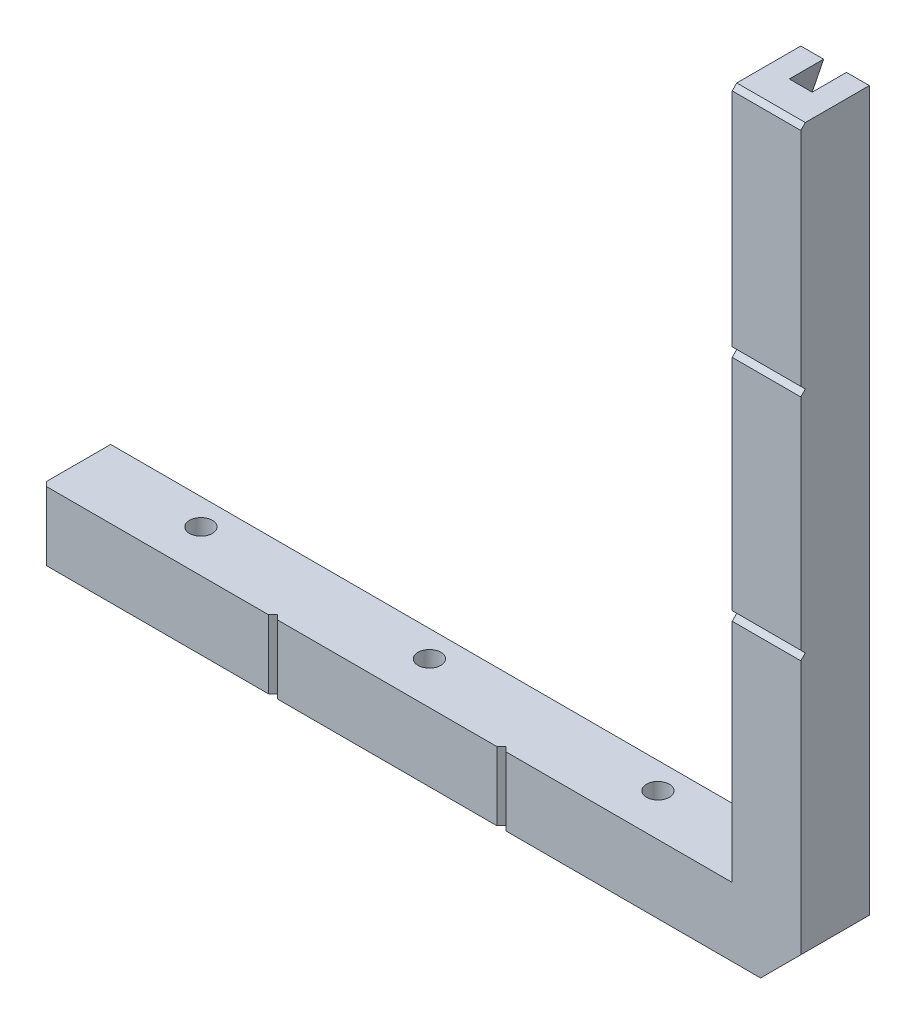
SolidWorks part; units mm, degrees
ref_plane "Front Plane" through (0, 0, 0) normal (0, 0, 1) x (1, 0, 0)
ref_plane "Top Plane" through (0, 0, 0) normal (0, 1, 0) x (1, 0, 0)
ref_plane "Right Plane" through (0, 0, 0) normal (1, 0, 0) x (0, 0, -1)
sketch "Sketch1" plane through (0, 0, 0) normal (0, 0, 1) x (1, 0, 0)
  line L0 (0, 0) -> (0, 151)
  line L1 (0, 151) -> (15, 151)
  line L2 (15, 151) -> (15, -15)
  line L3 (15, -15) -> (-151, -15)
  line L4 (-151, -15) -> (-151, 0)
  line L5 (-151, 0) -> (0, 0)
  dimension "D1" = 15
  dimension "D2" = 15
  dimension "D3" = 151
  dimension "D4" = 151
extrude "Boss-Extrude1" add sketch "Sketch1" along normal blind 15
sketch "Sketch3" plane through (0, 0, 15) normal (0, 0, 1) x (1, 0, 0)
  line L0 (-151, -7.5) -> (15, -7.5) construction
  line L1 (-151, 0) -> (-151, -15) construction
  line L2 (15, -15) -> (15, 151) construction
  line L3 (7.5, 151) -> (7.5, -15) construction
  line L4 (15, 151) -> (0, 151) construction
  line L5 (-151, -15) -> (15, -15) construction
  line L6 (0, 0) -> (-151, 0) construction
  line L7 (-51.5, -15) -> (-49.5, -15)
  line L8 (-51.5, -15) -> (-51.5, 0)
  line L9 (-51.5, 0) -> (-49.5, 0)
  line L10 (-49.5, -15) -> (-49.5, 0)
  line L11 (-51.5, -15) -> (-49.5, 0) construction
  line L12 (-51.5, 0) -> (-49.5, -15) construction
  line L13 (0, 151) -> (0, 0) construction
  line L15 (-101.5, -15) -> (-99.5, -15)
  line L16 (-101.5, -15) -> (-101.5, 0)
  line L17 (-101.5, 0) -> (-99.5, 0)
  line L18 (-99.5, -15) -> (-99.5, 0)
  line L19 (-101.5, -15) -> (-99.5, 0) construction
  line L20 (-101.5, 0) -> (-99.5, -15) construction
  line L27 (0, 51.5) -> (15, 51.5)
  line L28 (0, 51.5) -> (0, 49.5)
  line L29 (0, 49.5) -> (15, 49.5)
  line L30 (15, 51.5) -> (15, 49.5)
  line L31 (0, 51.5) -> (15, 49.5) construction
  line L32 (0, 49.5) -> (15, 51.5) construction
  line L33 (0, 101.5) -> (15, 101.5)
  line L34 (0, 101.5) -> (0, 99.5)
  line L35 (0, 99.5) -> (15, 99.5)
  line L36 (15, 101.5) -> (15, 99.5)
  line L37 (0, 101.5) -> (15, 99.5) construction
  line L38 (0, 99.5) -> (15, 101.5) construction
  point P12 (-50.5, -7.5)
  point P21 (-100.5, -7.5)
  point P30 (7.5, 50.5)
  point P35 (7.5, 100.5)
  dimension "D1" = 2
  dimension "D2" = 50.5
  dimension "D3" = 100.5
  dimension "D5" = 2
  dimension "D7" = 2
  dimension "D8" = 100.5
  dimension "D9" = 50.5
  dimension "D10" = 2
extrude "Cut-Extrude2" cut sketch "Sketch3" against normal blind 2
fillet "Fillet1" radius 2 8 edges at (-101.5, -7.5, 13) (-99.5, -7.5, 13) (-51.5, -7.5, 13) (-49.5, -7.5, 13) (7.5, 49.5, 13) (7.5, 51.5, 13) (7.5, 101.5, 13) (7.5, 99.5, 13) profile chamfer
sketch "Sketch4" plane through (0, -15, 0) normal (0, -1, 0) x (1, 0, 0)
  line L0 (-151, 15) -> (-151, 14)
  line L1 (-151, 15) -> (-151, 0) construction
  line L2 (-151, 14) -> (-150, 15)
  line L3 (-151, 15) -> (-101.5, 15) construction
  line L4 (-150, 15) -> (-151, 15)
  dimension "D1" = 1
  dimension "D2" = 1
extrude "Cut-Extrude3" cut sketch "Sketch4" against normal through all both and the other way through all
sketch "Sketch5" plane through (15, 0, 0) normal (1, 0, 0) x (0, 0, -1)
  line L0 (-15, 151) -> (-15, 150)
  line L1 (-15, 101.5) -> (-15, 151) construction
  line L2 (-15, 150) -> (-14, 151)
  line L3 (-15, 151) -> (0, 151) construction
  line L4 (-14, 151) -> (-15, 151)
  dimension "D1" = 1
  dimension "D2" = 1
extrude "Cut-Extrude4" cut sketch "Sketch5" against normal through all both and the other way through all
sketch "Sketch7" plane through (0, 0, 0) normal (-1, 0, 0) x (0, 0, 1)
  line L0 (5.75, 151) -> (5.75, -15) construction
  line L3 (14, 151) -> (0, 151) construction
  line L4 (14, -15) -> (0, -15) construction
  line L5 (0, 151) -> (0, 0) construction
  circle A0 centre (5.75, 75.5) radius 2.5
  circle A1 centre (5.75, 125.5) radius 2.5
  circle A2 centre (5.75, 25.5) radius 2.5
  dimension "D2" = 5
  dimension "D4" = 5
  dimension "D6" = 5
  dimension "D1" = 25
  dimension "D3" = 25
  dimension "D5" = 25
  dimension "D7" = 5.75
  dimension "D8" = 0
  dimension "D9" = 0
  dimension "D10" = 0
extrude "Cut-Extrude5" cut sketch "Sketch7" against normal blind 8
sketch "Sketch8" plane through (0, 0, 0) normal (0, 1, 0) x (1, 0, 0)
  line L0 (-151, -5.75) -> (0, -5.75) construction
  line L1 (-151, -14) -> (-151, 0) construction
  line L2 (0, -15) -> (0, 0) construction
  line L3 (0, 0) -> (-151, 0) construction
  circle A0 centre (-125.5, -5.75) radius 2.5
  circle A1 centre (-75.5, -5.75) radius 2.5
  circle A2 centre (-25.5, -5.75) radius 2.5
  dimension "D3" = 5
  dimension "D4" = 5
  dimension "D5" = 5
  dimension "D1" = 5.75
  dimension "D2" = 25
  dimension "D6" = 25
  dimension "D7" = 25
extrude "Cut-Extrude6" cut sketch "Sketch8" against normal blind 8
sketch "Sketch9" plane through (0, 0, 15) normal (0, 0, 1) x (1, 0, 0)
  line L0 (15, -6.2132) -> (6.2132, -15)
  line L1 (15, -15) -> (15, 49.5) construction
  line L2 (-49.5, -15) -> (15, -15) construction
  line L3 (6.2132, -15) -> (15, -15)
  line L4 (15, -15) -> (15, -6.2132)
  dimension "D1" = 15
extrude "Cut-Extrude7" cut sketch "Sketch9" against normal through all both and the other way through all
sketch "Sketch10" plane through (0, 0, 0) normal (0, 0, -1) x (-1, 0, 0)
  line L0 (151, -7.5) -> (129.292, -7.5) construction
  line L1 (151, 0) -> (151, -15) construction
  line L2 (151, -5) -> (143.5, -2.5)
  line L3 (143.5, -2.5) -> (143.5, -12.5)
  line L4 (143.5, -12.5) -> (151, -10)
  line L5 (151, -10) -> (151, -5)
  line L6 (-7.5, 151) -> (-7.5, 137.0187) construction
  line L7 (-15, 151) -> (0, 151) construction
  line L8 (-7.5, 151) -> (-10, 151)
  line L9 (-10, 151) -> (-12.5, 143.5)
  line L10 (-12.5, 143.5) -> (-7.5, 143.5)
  line L11 (-7.5, 143.5) -> (-2.5, 143.5)
  line L12 (-2.5, 143.5) -> (-5, 151)
  line L13 (-5, 151) -> (-7.5, 151)
  dimension "D1" = 2.5
  dimension "D2" = 2.5
  dimension "D3" = 5
  dimension "D4" = 5
  dimension "D5" = 2.5
  dimension "D6" = 2.5
  dimension "D7" = 5
  dimension "D8" = 5
  dimension "D9" = 7.5
  dimension "D10" = 7.5
extrude "Cut-Extrude8" cut sketch "Sketch10" against normal blind 7.5
